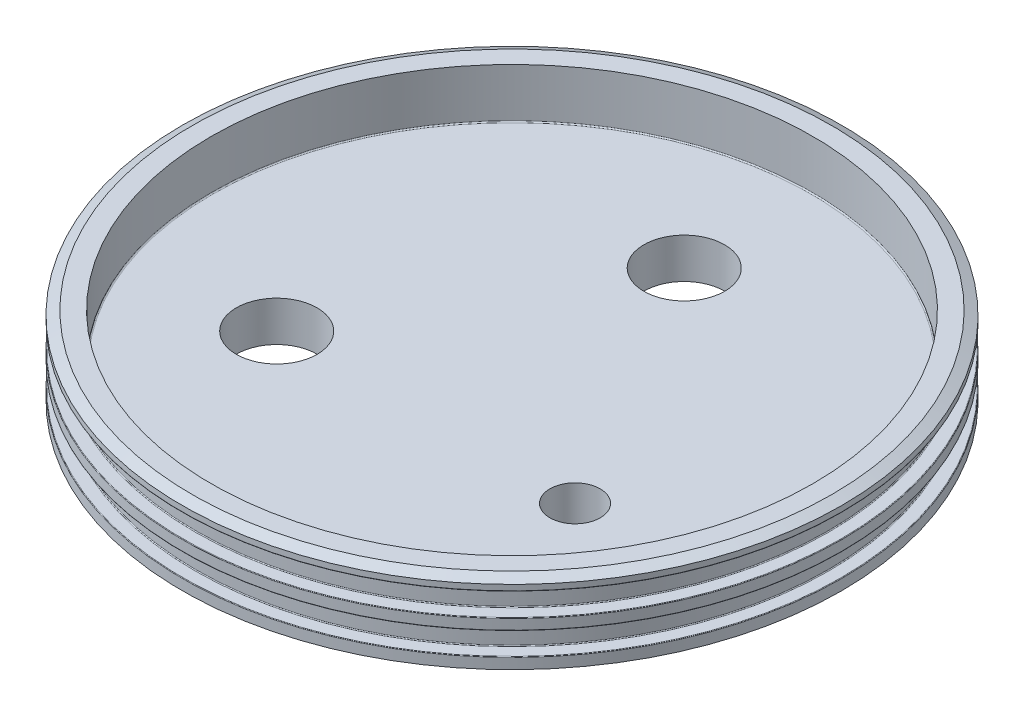
SolidWorks part; units mm, degrees
material "6061-T6 (SS)"
ref_plane "Front Plane" through (0, 0, 0) normal (0, 0, 1) x (1, 0, 0)
ref_plane "Top Plane" through (0, 0, 0) normal (0, 1, 0) x (1, 0, 0)
ref_plane "Right Plane" through (0, 0, 0) normal (1, 0, 0) x (0, 0, -1)
sketch "Sketch1" plane through (0, 0, 0) normal (0, 0, 1) x (1, 0, 0)
  line L0 (0, 48.1922) -> (0, -25.6743) construction
  line L1 (0, 0) -> (72.898, 0)
  line L2 (72.898, 0) -> (72.898, 2.4638)
  line L3 (72.898, 2.4638) -> (69.977, 2.4638)
  line L4 (69.977, 2.4638) -> (69.977, 7.4422)
  line L5 (69.977, 7.4422) -> (72.898, 7.4422)
  line L6 (72.898, 7.4422) -> (72.898, 9.906)
  line L7 (72.898, 9.906) -> (69.977, 9.906)
  line L8 (66.548, 17.3482) -> (66.548, 6.35)
  line L9 (66.548, 6.35) -> (0, 6.35)
  line L10 (0, 6.35) -> (0, 0)
  line L11 (69.977, 9.906) -> (69.977, 14.986)
  line L12 (69.977, 14.986) -> (72.898, 14.986)
  line L13 (72.898, 14.986) -> (72.898, 17.3482)
  line L14 (72.898, 17.3482) -> (66.548, 17.3482)
  dimension "D1" = 145.796
  dimension "D2" = 4.9784
  dimension "D3" = 2.921
  dimension "D4" = 9.906
  dimension "D5" = 6.35
  dimension "D6" = 6.35
  dimension "D7" = 5.08
  dimension "D8" = 9.906
revolve "Revolve1" add sketch "Sketch1" angle 360 about L0
sketch "Sketch6" plane through (0, 0, 0) normal (0, -1, 0) x (1, 0, 0)
  circle A0 centre (0, 0) radius 66.04
  dimension "D1" = 132.08
extrude "Boss-Extrude1" add sketch "Sketch6" along normal blind 2.54
fillet "CNC ID Fillet" radius 0.1778 5 edges at (-69.977, 7.4422, 0) (-69.977, 2.4638, 0) (66.04, 0, 0) (-69.977, 14.986, 0) (-69.977, 9.906, 0)
fillet "CNC OD Fillet" radius 0.127 5 edges at (-72.898, 7.4422, 0) (-72.898, 2.4638, 0) (-72.898, 9.906, 0) (-72.898, 14.986, 0) (66.04, -2.54, 0)
chamfer "CNC Chamfers" distance 1.016 angle 65 1 edges at (-72.898, 17.3482, 0) first distance on face at (-72.898, 15.113, 0)
fillet "CNC Bore Fillet" radius 0.254 1 edges at (-66.548, 6.35, 0)
hole_wizard "Pipe Tap Drill for 1/2 Tap - Fill Valve" positions "Sketch13" profile "Sketch14" hole size "1/2" standard "ANSI Inch" end condition through all
sketch "Sketch13" plane through (0, -2.54, 0) normal (0, -1, 0) x (-1, 0, 0)
  point P4 (0, 38.1)
  dimension "D1" = 38.1
sketch "Sketch14" plane through (0, -2.54, -38.1) normal (1, 0, 0) x (0, 0, -1)
  line L0 (0, 0) -> (0, 19.8882)
  line L1 (0, 19.8882) -> (8.9281, 19.8882)
  line L2 (8.9281, 19.8882) -> (8.9281, 0)
  line L5 (8.9281, 0) -> (0, 0)
  line L11 (0, -6.35) -> (0, 107.95) construction
  dimension "Thru Hole Dia." = 17.8562
  dimension "Thru Hole Depth" = 19.8882
hole_wizard "Pipe Tap Drill for 1/4 Tap - Solenoid Valve" positions "Sketch15" profile "Sketch16" hole size "1/4" standard "ANSI Inch" end condition through all
sketch "Sketch15" plane through (0, -2.54, 0) normal (0, -1, 0) x (-1, 0, 0)
  line L0 (-32.9956, -19.05) -> (0, -19.05) construction
  line L2 (-32.9956, -19.05) -> (0, 0) construction
  point P4 (-32.9956, -19.05)
  point P22 (0, 0)
  dimension "D1" = 30
  dimension "D2" = 38.1
sketch "Sketch16" plane through (32.9956, -2.54, 19.05) normal (1, 0, 0) x (0, 0, -1)
  line L0 (0, 0) -> (0, 19.8882)
  line L1 (0, 19.8882) -> (5.5626, 19.8882)
  line L2 (5.5626, 19.8882) -> (5.5626, 0)
  line L5 (5.5626, 0) -> (0, 0)
  line L11 (0, -6.35) -> (0, 107.95) construction
  dimension "Thru Hole Dia." = 11.1252
  dimension "Thru Hole Depth" = 19.8882
hole_wizard "Pipe Tap Drill for 1/2 Tap - Cryo Valve" positions "Sketch17" profile "Sketch18" hole size "1/2" standard "ANSI Inch" end condition through all
sketch "Sketch17" plane through (0, -2.54, 0) normal (0, -1, 0) x (-1, 0, 0)
  line L0 (32.9956, -19.05) -> (17.2813, -19.05) construction
  line L2 (32.9956, -19.05) -> (0, 0) construction
  point P4 (32.9956, -19.05)
  dimension "D1" = 30
  dimension "D2" = 38.1
sketch "Sketch18" plane through (-32.9956, -2.54, 19.05) normal (1, 0, 0) x (0, 0, -1)
  line L0 (0, 0) -> (0, 19.8882)
  line L1 (0, 19.8882) -> (8.9281, 19.8882)
  line L2 (8.9281, 19.8882) -> (8.9281, 0)
  line L5 (8.9281, 0) -> (0, 0)
  line L11 (0, -6.35) -> (0, 107.95) construction
  dimension "Thru Hole Dia." = 17.8562
  dimension "Thru Hole Depth" = 19.8882
